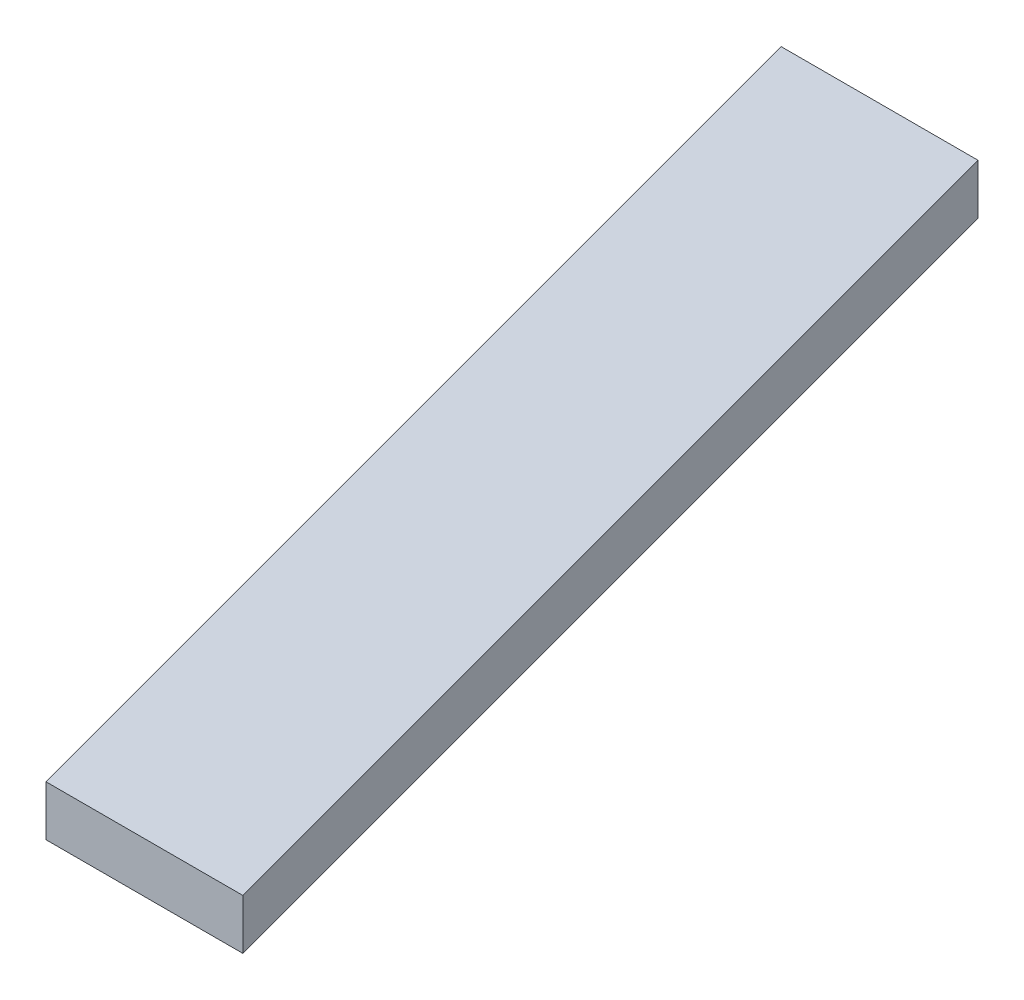
SolidWorks part; units mm, degrees
ref_plane "Front Plane" through (0, 0, 0) normal (0, 0, 1) x (1, 0, 0)
ref_plane "Top Plane" through (0, 0, 0) normal (0, 1, 0) x (1, 0, 0)
ref_plane "Right Plane" through (0, 0, 0) normal (1, 0, 0) x (0, 0, -1)
sketch "Sketch2" plane through (0, 0, 0) normal (0, 1, 0) x (1, 0, 0)
  line L0 (0, 0) -> (12.446, 0)
  line L1 (12.446, 0) -> (29.4608, -63.5)
  line L2 (29.4608, -63.5) -> (17.0148, -63.5)
  line L3 (17.0148, -63.5) -> (0, 0)
  dimension "D1" = 75
  dimension "D2" = 105
  dimension "D3" = 12.446
  dimension "D4" = 63.5
extrude "Boss-Extrude1" add sketch "Sketch2" along normal blind 3.175
